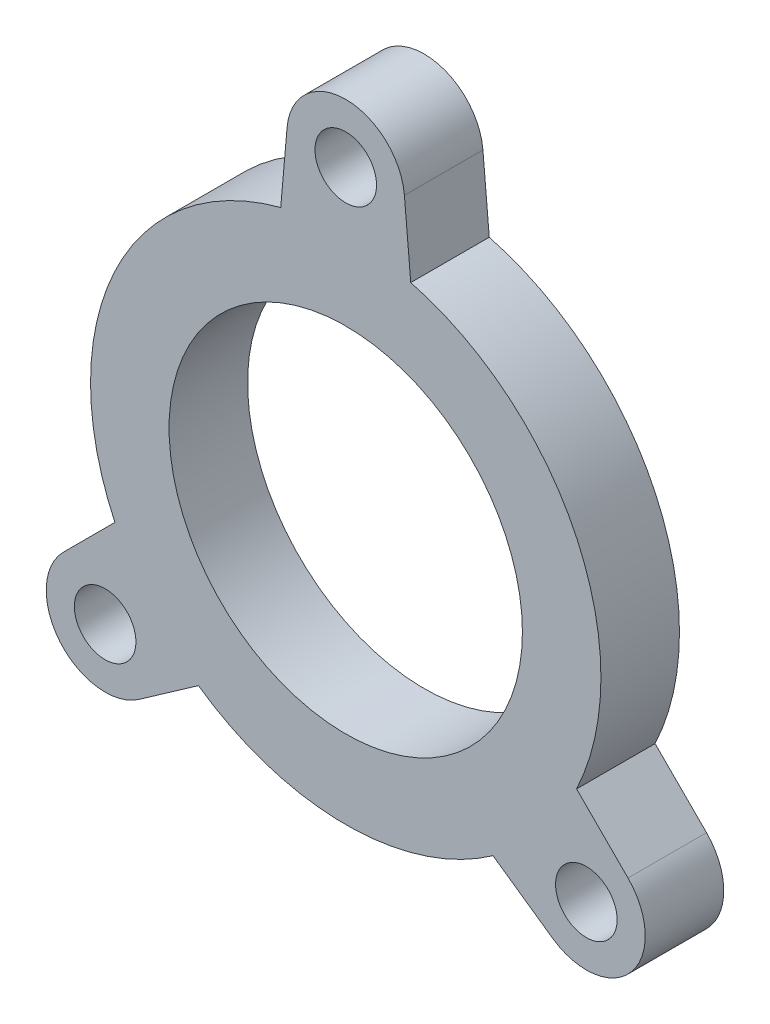
SolidWorks part; units mm, degrees
material "6061-T6 (SS)"
ref_plane "Front Plane" through (0, 0, 0) normal (0, 0, 1) x (1, 0, 0)
ref_plane "Top Plane" through (0, 0, 0) normal (0, 1, 0) x (1, 0, 0)
ref_plane "Right Plane" through (0, 0, 0) normal (1, 0, 0) x (0, 0, -1)
sketch "Sketch1" plane through (0, 0, 0) normal (0, 0, 1) x (1, 0, 0)
  line L0 (0, 0) -> (0, 25.4) construction
  line L1 (0, 0) -> (19.4575, -16.3268) construction
  line L2 (0, 0) -> (-19.4575, -16.3268) construction
  line L3 (-4.7444, 25.8151) -> (-5.2569, 19.9567)
  line L4 (4.7444, 25.8151) -> (5.2569, 19.9567)
  line L5 (22.8251, -12.9592) -> (18.6668, -8.8009)
  line L6 (16.7259, -20.228) -> (11.9087, -16.855)
  line L7 (-16.7259, -20.228) -> (-11.9087, -16.855)
  line L8 (-18.6668, -8.8009) -> (-22.8251, -12.9592)
  circle A0 centre (19.4575, -16.3268) radius 4.7625
  circle A1 centre (0, 25.4) radius 4.7625
  circle A2 centre (-19.4575, -16.3268) radius 4.7625
  circle A3 centre (19.4575, -16.3268) radius 2.4892
  circle A4 centre (-19.4575, -16.3268) radius 2.4892
  circle A5 centre (0, 25.4) radius 2.4892
  circle A6 centre (0, 0) radius 14.2875
  circle A7 centre (0, 0) radius 20.6375
  dimension "D1" = 9.525
  dimension "D4" = 4.9784
  dimension "D13" = 6.35
  dimension "D14" = 28.575
  dimension "D2" = 25.4
  dimension "D5" = 130
  dimension "D6" = 130
  dimension "D7" = 5
  dimension "D8" = 5
  dimension "D9" = 5
  dimension "D10" = 5
  dimension "D11" = 5
  dimension "D12" = 5
extrude "Boss-Extrude1" add sketch "Sketch1" along normal mid plane 6.35 contours A7 A6 | A7 L4 A1 L3 | A7 L6 A0 L5 | A7 L8 A2 L7 | A2 A4 | A1 A5 | A0 A3 | A7 A2 L7 | A7 L6 A0 | A7 A1 L3 region at (-3.9194, 21.5843, 0) region at (0, 30.0278, 0) region at (-2.5754, 19.8877, 0) region at (3.9194, 21.5843, 0) region at (-19.0539, -10.8717, 0) region at (-19.2557, -11.7034, 0) region at (-14.0152, -16.8766, 0) region at (19.0539, -10.8717, 0) region at (14.0152, -16.8766, 0) region at (23.7331, -14.5558, 0)
